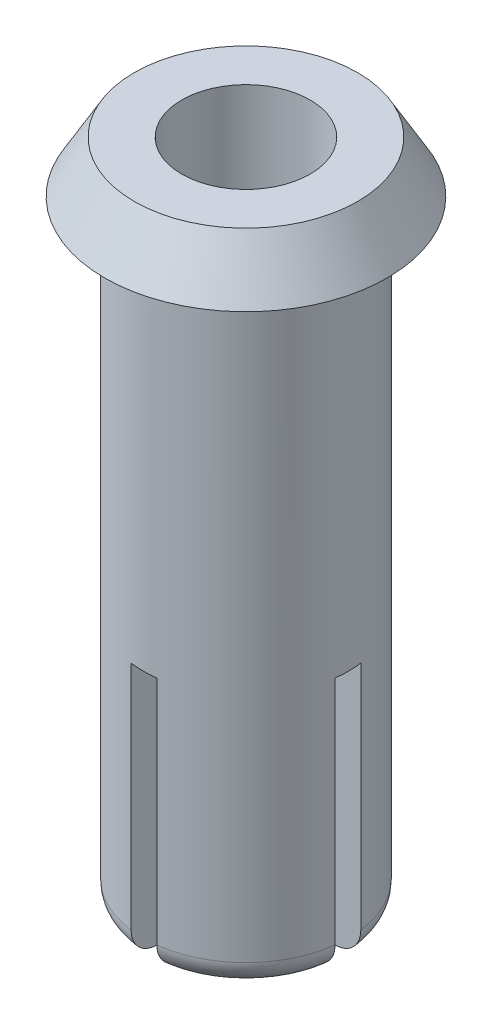
SolidWorks part; units mm, degrees
material "Nylon 6/10"
ref_plane "Face" through (0, 0, 0) normal (0, 0, 1) x (1, 0, 0)
ref_plane "Dessus" through (0, 0, 0) normal (0, 1, 0) x (1, 0, 0)
ref_plane "Droite" through (0, 0, 0) normal (1, 0, 0) x (0, 0, -1)
sketch "Esquisse1" plane through (0, 0, 0) normal (0, 1, 0) x (1, 0, 0)
  circle A0 centre (0, 0) radius 2
  dimension "D1" = 4
extrude "Boss.-Extru.1" add sketch "Esquisse1" along normal blind 13
sketch "Esquisse2" plane through (0, 13, 0) normal (0, 1, 0) x (1, 0, 0)
  circle A0 centre (0, 0) radius 2.75
  dimension "D1" = 5.5
extrude "Boss.-Extru.2" add sketch "Esquisse2" against normal blind 1
sketch "Esquisse3" plane through (0, 13, 0) normal (0, 1, 0) x (1, 0, 0)
  circle A0 centre (0, 0) radius 1.25
  dimension "D1" = 2.5
extrude "Enlèv. mat.-Extru.1" cut sketch "Esquisse3" against normal through all
chamfer "Chanfrein1" distance 1 angle 30 1 edges at (0, 13, 2.75) first distance on face at (0, 12, 2.75)
fillet "Congé2" radius 0.5 1 edges at (0, 0, 2)
sketch "Esquisse4" plane through (0, 0, 0) normal (0, -1, 0) x (1, 0, 0)
  line L2 (0.25, 1.9843) -> (0.25, 1.2247)
  line L3 (-0.25, 1.9843) -> (-0.25, 1.2247)
  line L4 (1.9843, 0.25) -> (1.2247, 0.25)
  line L5 (1.9843, -0.25) -> (1.2247, -0.25)
  line L7 (0, 1.25) -> (0, 2) construction
  line L9 (-1.2247, -0.25) -> (-1.9843, -0.25)
  line L10 (-1.2247, 0.25) -> (-1.9843, 0.25)
  line L12 (1.25, 0) -> (2, 0) construction
  line L14 (0.25, -1.2247) -> (0.25, -1.9843)
  line L15 (-0.25, -1.2247) -> (-0.25, -1.9843)
  circle A0 centre (0, 0) radius 2 construction
  circle A1 centre (0, 0) radius 1.25 construction
  arc A2 (0.25, 1.9843) -> (-0.25, 1.9843) centre (0, 0) ccw
  arc A3 (0.25, 1.2247) -> (-0.25, 1.2247) centre (0, 0) ccw
  arc A4 (-1.2247, 0.25) -> (-1.2247, -0.25) centre (0, 0) ccw
  arc A5 (-1.9843, 0.25) -> (-1.9843, -0.25) centre (0, 0) ccw
  arc A6 (-0.25, -1.9843) -> (0.25, -1.9843) centre (0, 0) ccw
  arc A7 (-0.25, -1.2247) -> (0.25, -1.2247) centre (0, 0) ccw
  arc A8 (1.2247, -0.25) -> (1.2247, 0.25) centre (0, 0) ccw
  arc A9 (1.9843, -0.25) -> (1.9843, 0.25) centre (0, 0) ccw
  dimension "D1" = 0.5
  dimension "D2" = 0.5
extrude "Enlèv. mat.-Extru.2" cut sketch "Esquisse4" against normal blind 5
